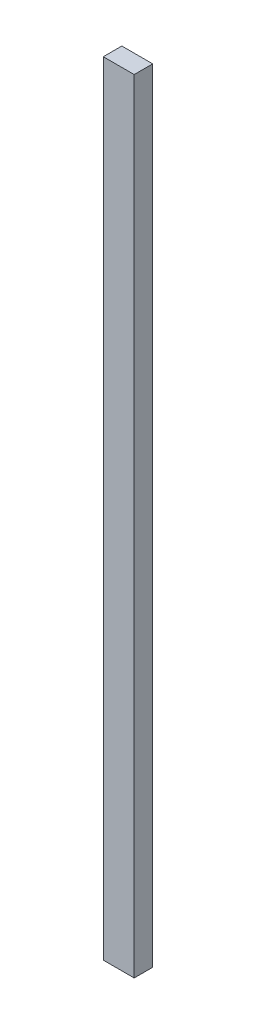
SolidWorks part; units mm, degrees
material "Plain Carbon Steel"
ref_plane "Front Plane" through (0, 0, 0) normal (0, 0, 1) x (1, 0, 0)
ref_plane "Top Plane" through (0, 0, 0) normal (0, 1, 0) x (1, 0, 0)
ref_plane "Right Plane" through (0, 0, 0) normal (1, 0, 0) x (0, 0, -1)
sketch "Sketch1" plane through (0, 0, 0) normal (0, 0, 1) x (1, 0, 0)
  line L1 (85, -11.4779) -> (55, -11.4779)
  line L2 (85, -11.4779) -> (85, -771.4779)
  line L3 (85, -771.4779) -> (55, -771.4779)
  line L4 (55, -11.4779) -> (55, -771.4779)
  line L5 (85, -11.4779) -> (55, -771.4779) construction
  line L6 (85, -771.4779) -> (55, -11.4779) construction
  line L7 (93, -771.4779) -> (47, -771.4779) construction
  point P0 (70, -391.4779)
  dimension "D1" = 30
extrude "Boss-Extrude1" add sketch "Sketch1" along normal blind 18
sketch "Center_lines" plane through (0, 0, 0) normal (0, 0, -1) x (-1, 0, 0)
  line L0 (-70, -11.4779) -> (-70, -771.4779) construction
  line L1 (-85, -11.4779) -> (-55, -11.4779) construction
  line L2 (-55, -771.4779) -> (-85, -771.4779) construction
  line L3 (-85, -391.4779) -> (-55, -391.4779) construction
  line L4 (-85, -771.4779) -> (-85, -11.4779) construction
  line L5 (-55, -11.4779) -> (-55, -771.4779) construction
sketch "Center_lines_top" plane through (0, 0, 18) normal (0, 0, 1) x (1, 0, 0)
  line L0 (70, -11.4779) -> (70, -771.4779) construction
  line L1 (55, -391.4779) -> (85, -391.4779) construction
  point P8 (70, -391.4779)
